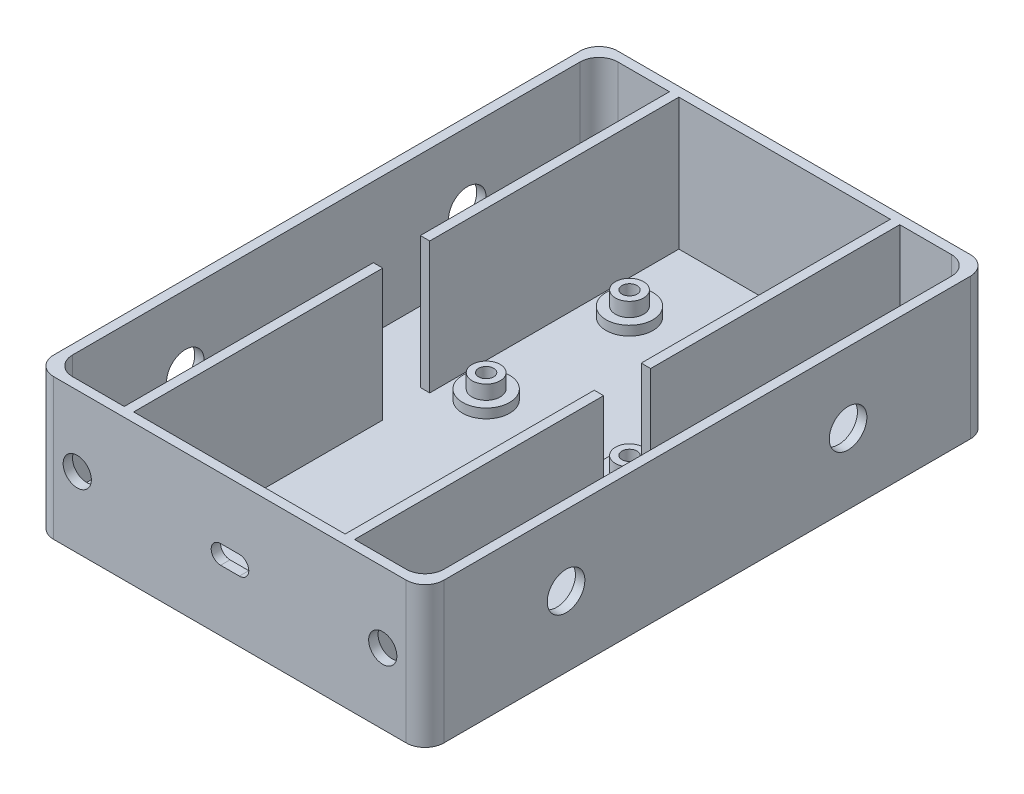
SolidWorks part; units mm, degrees
ref_plane "Front Plane" through (0, 0, 0) normal (0, 0, 1) x (1, 0, 0)
ref_plane "Top Plane" through (0, 0, 0) normal (0, 1, 0) x (1, 0, 0)
ref_plane "Right Plane" through (0, 0, 0) normal (1, 0, 0) x (0, 0, -1)
sketch "Sketch2" plane through (0, 0, 0) normal (0, 0, 1) x (1, 0, 0)
  line L0 (-41.5, -15) -> (41.5, 15) construction
  line L1 (-41.5, 15) -> (41.5, 15)
  line L2 (-41.5, 15) -> (-41.5, -15)
  line L3 (-41.5, -15) -> (41.5, -15)
  line L4 (41.5, 15) -> (41.5, -15)
  line L5 (41.5, -15) -> (-41.5, 15) construction
  point P4 (0, 0)
  dimension "D1" = 30
  dimension "D2" = 83
extrude "Boss-Extrude1" add sketch "Sketch2" against normal blind 120
sketch "Sketch4" plane through (0, 15, 0) normal (0, 1, 0) x (1, 0, 0)
  line L0 (-41.5, 120) -> (-41.5, 0) construction
  line L1 (-39.5, 118) -> (-24.5, 118)
  line L2 (-39.5, 118) -> (-39.5, 2)
  line L3 (-39.5, 2) -> (39.5, 2)
  line L4 (39.5, 118) -> (39.5, 2)
  line L5 (41.5, 120) -> (41.5, 0) construction
  line L6 (41.5, 120) -> (-41.5, 120) construction
  line L7 (41.5, 0) -> (-41.5, 0) construction
  line L8 (-39.5, 60) -> (39.5, 60) construction
  line L9 (-24.5, 118) -> (-22.5, 118)
  line L10 (-24.5, 118) -> (-24.5, 65)
  line L11 (-24.5, 65) -> (-22.5, 65)
  line L12 (-22.5, 118) -> (-22.5, 65)
  line L13 (22.5, 118) -> (24.5, 118)
  line L14 (22.5, 118) -> (22.5, 65)
  line L15 (22.5, 65) -> (24.5, 65)
  line L16 (24.5, 118) -> (24.5, 65)
  line L17 (-24.5, 2) -> (-22.5, 2)
  line L18 (-24.5, 2) -> (-24.5, 55)
  line L19 (-24.5, 55) -> (-22.5, 55)
  line L20 (-22.5, 2) -> (-22.5, 55)
  line L21 (22.5, 2) -> (24.5, 2)
  line L22 (22.5, 2) -> (22.5, 55)
  line L23 (22.5, 55) -> (24.5, 55)
  line L24 (24.5, 2) -> (24.5, 55)
  line L25 (-22.5, 118) -> (39.5, 118)
  arc A0 (-39.5, 109.5) -> (-31, 118) centre (-39.5, 118) ccw
  arc A1 (31, 118) -> (39.5, 109.5) centre (39.5, 118) ccw
  arc A2 (39.5, 10.5) -> (31, 2) centre (39.5, 2) ccw
  arc A3 (-31, 2) -> (-39.5, 10.5) centre (-39.5, 2) ccw
  dimension "D12" = 17
  dimension "D14" = 17
  dimension "D15" = 17
  dimension "D13" = 17
  dimension "D1" = 2
  dimension "D2" = 2
  dimension "D3" = 2
  dimension "D4" = 2
  dimension "D5" = 2
  dimension "D6" = 2
  dimension "D7" = 15
  dimension "D8" = 15
  dimension "D9" = 5
  dimension "D10" = 5
  dimension "D11" = 53
extrude "Cut-Extrude1" cut sketch "Sketch4" against normal blind 28 contours L8 L2 L3 L18 L19 L20 L22 L23 L24 L4 | L2 L8 L4 L25 L16 L15 L14 L12 L11 L10 L1 region at (0, 15, -88.1985) region at (0, 15, -31.8015)
sketch "Sketch5" [suppressed] plane through (0, 0, 0) normal (0, 0, 1) x (1, 0, 0)
  line L0 (-39.5, 16) -> (-39.5, -16) construction
  line L1 (-41.5, -16) -> (41.5, -16) construction
  line L2 (39.5, 16) -> (39.5, -16)
  line L3 (-24.5, 16) -> (-24.5, -16)
  line L4 (41.5, 16) -> (-41.5, 16) construction
  line L5 (-39.5, 16) -> (-24.5, -16) construction
  line L6 (-24.5, 16) -> (-39.5, -16) construction
  line L7 (-41.5, 16) -> (-41.5, -16) construction
  line L8 (41.5, -16) -> (41.5, 16) construction
  line L9 (24.5, 16) -> (24.5, -16) construction
  line L10 (24.5, 16) -> (39.5, -16) construction
  line L11 (24.5, -16) -> (39.5, 16) construction
  circle A0 centre (-32, 0) radius 3
  circle A1 centre (32, 0) radius 3
  dimension "D2" = 6
  dimension "D6" = 6
  dimension "D1" = 15
  dimension "D3" = 2
  dimension "D4" = 2
  dimension "D5" = 15
extrude "Cut-Extrude3" [suppressed] cut sketch "Sketch5" against normal through all contours A0 | A1
sketch "Sketch6" plane through (0, 0, 0) normal (0, 0, 1) x (1, 0, 0)
  line L0 (-41.5, 15) -> (41.5, -15) construction
  line L1 (-2, 0) -> (2, 0) construction
  line L2 (41.5, 15) -> (-41.5, -15) construction
  line L3 (-2, 2) -> (2, 2)
  line L4 (-2, -2) -> (2, -2)
  arc A1 (-2, 2) -> (-2, -2) centre (-2, 0) ccw
  arc A2 (2, -2) -> (2, 2) centre (2, 0) ccw
  point P13 (0, 0)
extrude "Cut-Extrude4" cut sketch "Sketch6" against normal up to next
sketch "Sketch10" plane through (0, -13, 0) normal (0, 1, 0) x (1, 0, 0)
  line L0 (0, 118) -> (0, 2) construction
  line L1 (-22.5, 118) -> (22.5, 118) construction
  line L2 (-22.5, 2) -> (22.5, 2) construction
  line L3 (-18, 103) -> (18, 67) construction
  line L4 (-18, 103) -> (18, 103) construction
  line L5 (-18, 103) -> (-18, 67) construction
  line L6 (-18, 67) -> (18, 67) construction
  line L7 (18, 103) -> (18, 67) construction
  line L8 (18, 103) -> (-18, 67) construction
  circle A0 centre (-15.25, 100.25) radius 1.6
  circle A1 centre (15.25, 100.25) radius 1.6
  circle A2 centre (-15.25, 69.75) radius 1.6
  circle A3 centre (15.25, 69.75) radius 1.6
  circle A4 centre (-15.25, 100.25) radius 3
  circle A5 centre (15.25, 100.25) radius 3
  circle A6 centre (15.25, 69.75) radius 3
  circle A7 centre (-15.25, 69.75) radius 3
  point P10 (0, 85)
  point P11 (0, 103)
  point P12 (0, 103)
  dimension "D4" = 30.5
  dimension "D8" = 6
  dimension "D9" = 3.2
  dimension "D10" = 6
  dimension "D11" = 3.2
  dimension "D12" = 3.2
  dimension "D13" = 6
  dimension "D14" = 3.2
  dimension "D15" = 6
  dimension "D1" = 36
  dimension "D2" = 36
  dimension "D3" = 15
  dimension "D5" = 30.5
  dimension "D6" = 15.25
  dimension "D7" = 15.25
extrude "Boss-Extrude2" add sketch "Sketch10" along normal blind 5
sketch "Sketch13" plane through (0, -13, 0) normal (0, 1, 0) x (1, 0, 0)
  circle A0 centre (-15.25, 100.25) radius 5
  circle A1 centre (15.25, 100.25) radius 5
  circle A2 centre (-15.25, 69.75) radius 5
  circle A3 centre (15.25, 69.75) radius 5
  dimension "D1" = 10
  dimension "D2" = 10
  dimension "D3" = 10
  dimension "D4" = 10
extrude "Boss-Extrude-cc3d-support" add sketch "Sketch13" along normal blind 2
sketch "Sketch11" [suppressed] plane through (0, -14, 0) normal (0, 1, 0) x (1, 0, 0)
  line L1 (-15.25, 96.9591) -> (-12.4, 98.6046)
  line L2 (-12.4, 98.6046) -> (-12.4, 101.8954)
  line L3 (-12.4, 101.8954) -> (-15.25, 103.5409)
  line L4 (-15.25, 103.5409) -> (-18.1, 101.8954)
  line L5 (-18.1, 101.8954) -> (-18.1, 98.6046)
  line L6 (-18.1, 98.6046) -> (-15.25, 96.9591)
  line L7 (12.4, 98.6046) -> (15.25, 96.9591)
  line L8 (15.25, 96.9591) -> (18.1, 98.6046)
  line L9 (18.1, 98.6046) -> (18.1, 101.8954)
  line L10 (18.1, 101.8954) -> (15.25, 103.5409)
  line L11 (15.25, 103.5409) -> (12.4, 101.8954)
  line L12 (12.4, 101.8954) -> (12.4, 98.6046)
  line L13 (-12.4, 68.1046) -> (-12.4, 71.3954)
  line L14 (-12.4, 71.3954) -> (-15.25, 73.0409)
  line L15 (-15.25, 73.0409) -> (-18.1, 71.3954)
  line L16 (-18.1, 71.3954) -> (-18.1, 68.1046)
  line L17 (-18.1, 68.1046) -> (-15.25, 66.4591)
  line L18 (-15.25, 66.4591) -> (-12.4, 68.1046)
  line L19 (12.4, 68.1046) -> (15.25, 66.4591)
  line L20 (15.25, 66.4591) -> (18.1, 68.1046)
  line L21 (18.1, 68.1046) -> (18.1, 71.3954)
  line L22 (18.1, 71.3954) -> (15.25, 73.0409)
  line L23 (15.25, 73.0409) -> (12.4, 71.3954)
  line L24 (12.4, 71.3954) -> (12.4, 68.1046)
  circle A0 centre (-15.25, 100.25) radius 2.85 construction
  circle A1 centre (15.25, 100.25) radius 2.85 construction
  circle A2 centre (-15.25, 69.75) radius 2.85 construction
  circle A3 centre (15.25, 69.75) radius 2.85 construction
  dimension "D1" = 5.7
  dimension "D2" = 5.7
  dimension "D3" = 5.7
  dimension "D4" = 5.7
extrude "Cut-Extrude7" [suppressed] cut sketch "Sketch11" against normal up to next and the other way blind 1
extrude "Cut-Extrude-cc3d-round" cut sketch "Sketch10<3>" against normal blind 5 and the other way blind 10 contours A0 | A1 | A3 | A2
sketch "Sketch10<3>" plane through (0, -13, 0) normal (0, 1, 0) x (1, 0, 0) same geometry as "Sketch10"
sketch "Sketch14" plane through (0, -15, 0) normal (0, -1, 0) x (1, 0, 0)
  line L0 (-41.5, -120) -> (41.5, -120) construction
  line L1 (-36.65, -8.5818) -> (-33.8, -6.9363)
  line L2 (-33.8, -6.9363) -> (-33.8, -3.6454)
  line L3 (-33.8, -3.6454) -> (-36.65, -2)
  line L4 (-36.65, -2) -> (-39.5, -3.6454)
  line L5 (-39.5, -3.6454) -> (-39.5, -6.9363)
  line L6 (-39.5, -6.9363) -> (-36.65, -8.5818)
  line L7 (36.65, -118) -> (39.5, -116.3546)
  line L8 (-41.5, 0) -> (41.5, 0) construction
  line L9 (-41.5, -120) -> (-41.5, 0) construction
  line L10 (41.5, -120) -> (41.5, 0) construction
  line L11 (36.65, -8.5818) -> (39.5, -6.9363)
  line L12 (39.5, -6.9363) -> (39.5, -3.6454)
  line L13 (39.5, -3.6454) -> (36.65, -2)
  line L14 (36.65, -2) -> (33.8, -3.6454)
  line L15 (33.8, -3.6454) -> (33.8, -6.9363)
  line L16 (33.8, -6.9363) -> (36.65, -8.5818)
  line L17 (39.5, -116.3546) -> (39.5, -113.0637)
  line L18 (39.5, -113.0637) -> (36.65, -111.4182)
  line L19 (36.65, -111.4182) -> (33.8, -113.0637)
  line L20 (33.8, -113.0637) -> (33.8, -116.3546)
  line L21 (33.8, -116.3546) -> (36.65, -118)
  line L22 (-15.25, -69.75) -> (15.25, -69.75) construction
  line L23 (-36.65, -118) -> (-33.8, -116.3546)
  line L24 (-33.8, -116.3546) -> (-33.8, -113.0637)
  line L25 (-33.8, -113.0637) -> (-36.65, -111.4182)
  line L26 (-36.65, -111.4182) -> (-39.5, -113.0637)
  line L27 (-39.5, -113.0637) -> (-39.5, -116.3546)
  line L28 (-39.5, -116.3546) -> (-36.65, -118)
  line L29 (-15.25, -73.0409) -> (-12.4, -71.3954)
  line L30 (-12.4, -71.3954) -> (-12.4, -68.1046)
  line L31 (-12.4, -68.1046) -> (-15.25, -66.4591)
  line L32 (-15.25, -66.4591) -> (-18.1, -68.1046)
  line L33 (-18.1, -68.1046) -> (-18.1, -71.3954)
  line L34 (-18.1, -71.3954) -> (-15.25, -73.0409)
  line L35 (15.25, -73.0409) -> (18.1, -71.3954)
  line L36 (18.1, -71.3954) -> (18.1, -68.1046)
  line L37 (18.1, -68.1046) -> (15.25, -66.4591)
  line L38 (15.25, -66.4591) -> (12.4, -68.1046)
  line L39 (12.4, -68.1046) -> (12.4, -71.3954)
  line L40 (12.4, -71.3954) -> (15.25, -73.0409)
  line L41 (15.25, -103.5409) -> (18.1, -101.8954)
  line L42 (18.1, -101.8954) -> (18.1, -98.6046)
  line L43 (18.1, -98.6046) -> (15.25, -96.9591)
  line L44 (15.25, -96.9591) -> (12.4, -98.6046)
  line L45 (12.4, -98.6046) -> (12.4, -101.8954)
  line L46 (12.4, -101.8954) -> (15.25, -103.5409)
  line L47 (-15.25, -103.5409) -> (-12.4, -101.8954)
  line L48 (-12.4, -101.8954) -> (-12.4, -98.6046)
  line L49 (-12.4, -98.6046) -> (-15.25, -96.9591)
  line L50 (-15.25, -96.9591) -> (-18.1, -98.6046)
  line L51 (-18.1, -98.6046) -> (-18.1, -101.8954)
  line L52 (-18.1, -101.8954) -> (-15.25, -103.5409)
  line L53 (15.25, -69.75) -> (15.25, -100.25) construction
  line L54 (15.25, -100.25) -> (-15.25, -100.25) construction
  line L55 (-15.25, -100.25) -> (-15.25, -69.75) construction
  line L56 (-41.5, 0) -> (41.5, 0) construction
  line L57 (-41.5, -120) -> (-41.5, 0) construction
  circle A0 centre (-36.65, -5.2909) radius 2.85 construction
  circle A1 centre (-36.65, -5.2909) radius 1.6
  circle A2 centre (36.65, -5.2909) radius 2.85 construction
  circle A3 centre (36.65, -5.2909) radius 1.6
  circle A4 centre (36.65, -114.7091) radius 2.85 construction
  circle A5 centre (36.65, -114.7091) radius 1.6
  circle A6 centre (-36.65, -114.7091) radius 2.85 construction
  circle A7 centre (-36.65, -114.7091) radius 1.6
  circle A8 centre (-15.25, -69.75) radius 2.85 construction
  circle A9 centre (15.25, -69.75) radius 2.85 construction
  circle A10 centre (15.25, -100.25) radius 2.85 construction
  circle A11 centre (-15.25, -100.25) radius 2.85 construction
  circle A12 centre (-15.25, -100.25) radius 1.6
  circle A13 centre (15.25, -100.25) radius 1.6
  circle A14 centre (15.25, -69.75) radius 1.6
  circle A15 centre (-15.25, -69.75) radius 1.6
  circle M72 centre (15.25, -69.75) radius 1.6
  circle M73 centre (-15.25, -100.25) radius 1.6
  circle M74 centre (15.25, -100.25) radius 1.6
  circle M75 centre (-15.25, -69.75) radius 1.6
  dimension "D2" = 3.2
  dimension "D8" = 3.2
  dimension "D12" = 3.2
  dimension "D16" = 3.2
  dimension "D21" = 3.2
  dimension "D22" = 3.2
  dimension "D23" = 3.2
  dimension "D24" = 3.2
  dimension "D1" = 5.7
  dimension "D3" = 5.7
  dimension "D4" = 2
  dimension "D5" = 2
  dimension "D6" = 2
  dimension "D7" = 2
  dimension "D9" = 5.7
  dimension "D10" = 2
  dimension "D11" = 2
  dimension "D13" = 5.7
  dimension "D14" = 2
  dimension "D15" = 2
  dimension "D17" = 5.7
  dimension "D18" = 5.7
  dimension "D19" = 5.7
  dimension "D20" = 5.7
  dimension "D25" = 5.2909
  dimension "D26" = 4.85
extrude "Cut-Extrude-bottom-hex-corners" cut sketch "Sketch14" against normal blind 3.5 contours L27 L28 L23 L24 L25 L26 A7 | L20 L21 L7 L17 L18 L19 A5 | L15 L16 L11 L12 L13 L14 A3 | L5 L6 L1 L2 L3 L4 A1 region at (-38.0315, -15, -7.6837) region at (35.2685, -15, -117.1019) region at (35.2685, -15, -7.6837) region at (-38.0315, -15, -117.1019)
extrude "Cut-Extrude-bottom-hex-cc3d" cut sketch "Sketch14<5>" against normal blind 2.5 contours L51 L52 L47 L48 L49 L50 M73 | L33 L34 L29 L30 L31 L32 M75 | L39 L40 L35 L36 L37 L38 M72 | L45 L46 L41 L42 L43 L44 M74 region at (-16.6315, -15, -72.1428) region at (13.8685, -15, -72.1428) region at (13.8685, -15, -102.6428) region at (-16.6315, -15, -102.6428)
sketch "Sketch14<5>" plane through (0, -15, 0) normal (0, -1, 0) x (1, 0, 0) same geometry as "Sketch14"
extrude "Cut-Extrude-bottom-round" cut sketch "Sketch14<4>" against normal through all contours A7 | A5 | A3 | A1
sketch "Sketch14<4>" plane through (0, -15, 0) normal (0, -1, 0) x (1, 0, 0) same geometry as "Sketch14"
extrude "Cut-Extrude12" cut sketch "Sketch4<5>" against normal blind 25 contours L2 A0 L1 | L25 A1 L4 | L4 A2 L3 | L3 A3 L2 region at (-35.8925, 15, -114.3925) region at (-35.8925, 15, -5.6075) region at (35.8925, 15, -114.3925) region at (35.8925, 15, -5.6075)
sketch "Sketch4<5>" plane through (0, 15, 0) normal (0, 1, 0) x (1, 0, 0) same geometry as "Sketch4"
sketch "Sketch8" plane through (41.5, 0, 0) normal (1, 0, 0) x (0, 0, -1)
  line L0 (60, 15) -> (60, -15) construction
  line L1 (120, 15) -> (0, 15) construction
  line L2 (120, -15) -> (0, -15) construction
  line L3 (30, 15) -> (30, -15) construction
  line L4 (0, -15) -> (0, 15) construction
  line L5 (90, 15) -> (90, -15)
  circle A1 centre (30, 0) radius 4
  circle A2 centre (90, 0) radius 4
  dimension "D5" = 8
  dimension "D6" = 8
  dimension "D1" = 30
  dimension "D2" = 30
  dimension "D3" = 30
extrude "Cut-Holes-Right" cut sketch "Sketch8" against normal up to next contours A1 | A2
extrude "Cut-Holes-Left" cut sketch "Sketch8<4>" along normal up to next from surface contours A1 | A2 starting at face at (-41.5, 0, -60)
sketch "Sketch8<4>" plane through (41.5, 0, 0) normal (1, 0, 0) x (0, 0, -1) same geometry as "Sketch8"
fillet "Fillet1_4mm" radius 4 8 edges at (41.5, 0, -120) (-39.5, 2.5, -118) (39.5, 2.5, -118) (39.5, 2.5, -2) (-41.5, 0, -120) (-39.5, 2.5, -2) (41.5, 0, 0) (-41.5, 0, 0)
fillet "Fillet2" [suppressed] radius 2
sketch "Sketch15" plane through (0, 0, 0) normal (0, 0, 1) x (1, 0, 0)
  line L1 (-37.5, -15) -> (37.5, -15) construction
  line L2 (-37.5, 15) -> (-37.5, -15) construction
  line L3 (37.5, -15) -> (37.5, 15) construction
  circle A0 centre (-32.5, 0) radius 3
  circle A1 centre (32.5, 0) radius 3
  dimension "D1" = 15
  dimension "D5" = 6
  dimension "D6" = 6
  dimension "D2" = 15
  dimension "D3" = 5
  dimension "D4" = 5
extrude "Cut-Extrude14" cut sketch "Sketch15" against normal up to next
extrude "Cut-Extrude15" cut sketch "Sketch15<2>" along normal up to next from surface starting at face at (0, 0, -120)
sketch "Sketch15<2>" plane through (0, 0, 0) normal (0, 0, 1) x (1, 0, 0) same geometry as "Sketch15"
